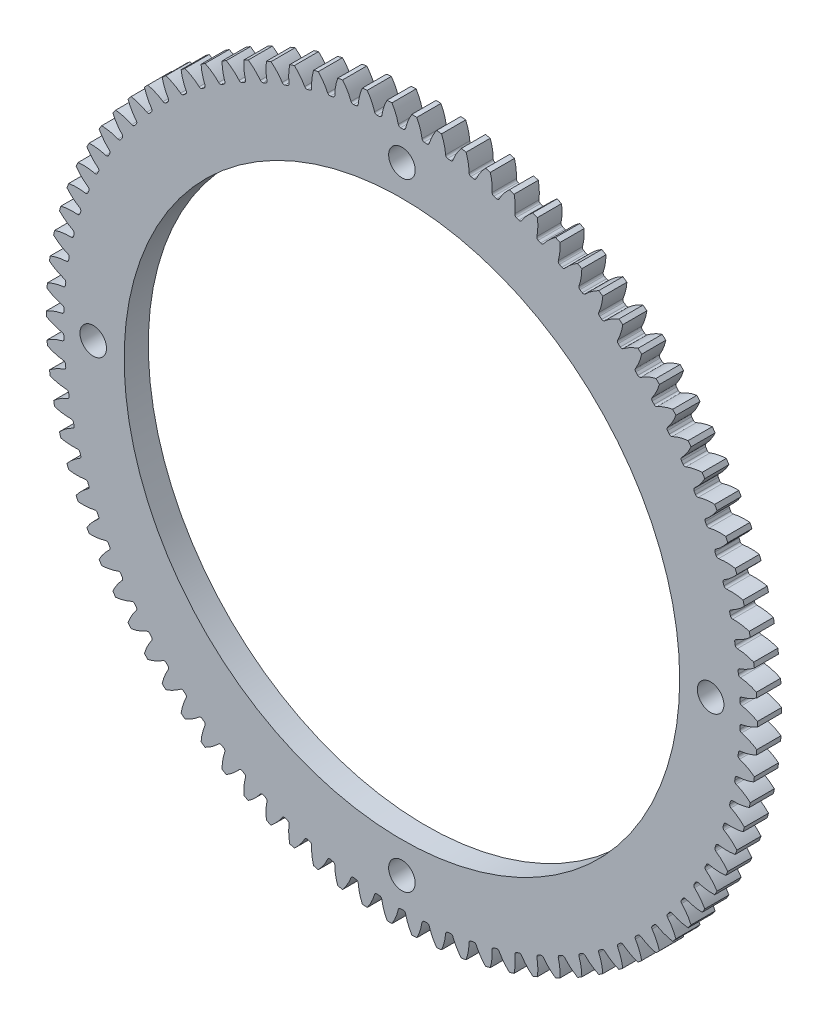
SolidWorks part; units mm, degrees
ref_plane "Front Plane" through (0, 0, 0) normal (0, 0, 1) x (1, 0, 0)
ref_plane "Top Plane" through (0, 0, 0) normal (0, 1, 0) x (1, 0, 0)
ref_plane "Right Plane" through (0, 0, 0) normal (1, 0, 0) x (0, 0, -1)
sketch "Sketch2" plane through (0, 0, 0) normal (0, 0, 1) x (1, 0, 0)
  circle A0 centre (0, 0) radius 72 construction
  circle A1 centre (0, 0) radius 73.6
  dimension "D1" = 144
  dimension "D2" = 147.2
extrude "Boss-Extrude1" add sketch "Sketch2" against normal blind 5
sketch "Sketch3" plane through (0, 0, 0) normal (0, 0, 1) x (1, 0, 0)
  line L0 (0, 73.6) -> (0, 0) construction
  line L1 (0, 0) -> (5.1341, 73.4207) construction
  line L2 (0, 0) -> (2.5686, 73.5552) construction
  line L4 (-1.2566, 71.989) -> (1.2566, 71.989) construction
  line L5 (1.2566, 71.989) -> (3.7682, 71.9013) construction
  line L6 (-1.8976, 73.5755) -> (0, 68.8789) construction
  arc A0 (0.6782, 69.9967) -> (-0.6782, 69.9967) centre (0, 0) ccw
  circle A1 centre (0, 0) radius 70.4 construction
  circle A2 centre (0, 0) radius 73.6 construction
  arc A3 (-2.0617, 73.5711) -> (-0.6782, 69.9967) centre (-10.7538, 68.1519) cw
  arc A4 (2.0617, 73.5711) -> (0.6782, 69.9967) centre (10.7538, 68.1519) ccw
  circle A5 centre (0, 0) radius 73.6 construction
  circle A6 centre (0, 0) radius 72 construction
  arc A8 (2.0617, 73.5711) -> (-2.0617, 73.5711) centre (0, 0) ccw
  dimension "D2" = 3.2
  dimension "D3" = 3.6
  dimension "D4" = 22
  dimension "D5" = 0.4
extrude "Cut-Extrude1" cut sketch "Sketch3" against normal blind 25
fillet "Fillet1" radius 0.48 2 edges at (0.6782, 69.9967, -2.5) (-0.6782, 69.9967, -2.5)
pattern_circular "CirPattern1" count 90 over 360 about axis through (0, 0, 0) along (0, 0, 1) of "Fillet1", "Cut-Extrude1"
sketch "Sketch4" plane through (0, 0, 0) normal (0, 0, 1) x (1, 0, 0)
  circle A0 centre (0, 0) radius 4.1
  dimension "D1" = 8.2
extrude "Cut-Extrude2" cut sketch "Sketch4" against normal through all both and the other way through all
sketch "Sketch6" plane through (0, 0, 0) normal (0, 0, 1) x (1, 0, 0)
  circle A0 centre (0, 0) radius 12 construction
  circle A1 centre (0, 12) radius 1.5
  dimension "D1" = 24
  dimension "D2" = 3
extrude "Cut-Extrude4" cut sketch "Sketch6" against normal through all both and the other way through all
pattern_circular "CirPattern2" count 4 every 90 about axis through (0, 0, 0) along (0, 0, 1) of "Cut-Extrude4"
sketch "Sketch7" plane through (0, 0, 0) normal (0, 0, 1) x (1, 0, 0)
  circle A0 centre (0, 0) radius 16.5
  dimension "D1" = 33
extrude "Cut-Extrude5" cut sketch "Sketch7" against normal blind 3.2
sketch "Sketch8" plane through (0, 0, 0) normal (0, 0, 1) x (1, 0, 0)
  circle A0 centre (0, 0) radius 57.5
  dimension "D1" = 115
extrude "Cut-Extrude6" cut sketch "Sketch8" against normal through all
sketch "Sketch10" plane through (0, 0, 0) normal (0, 0, 1) x (1, 0, 0)
  circle A0 centre (0, 63.9) radius 2.75
  dimension "D1" = 5.5
  dimension "D2" = 63.9
extrude "Cut-Extrude7" cut sketch "Sketch10" against normal through all contours A0
pattern_circular "CirPattern3" count 4 over 360 about axis through (0, 0, 0) along (0, 0, 1) of "Cut-Extrude7"
equation "\"module\"= 1.6"
equation "\"teeth\"= 90"
equation "\"pressure angle\"= 22"
equation "\"D1@Sketch2\"=\"module\"*\"teeth\""
equation "\"D2@Sketch2\"=(\"teeth\"+2)*\"module\""
equation "\"D1@Sketch3\"=360/\"teeth\""
equation "\"D2@Sketch3\"=\"module\"*2"
equation "\"D3@Sketch3\"=\"module\"*if( \"module\"=>1.25,2.25,2.4)"
equation "\"D4@Sketch3\"=\"pressure angle\""
equation "\"D1@Fillet1\"=0.3*\"module\""
equation "\"D1@CirPattern1\"=\"teeth\""
